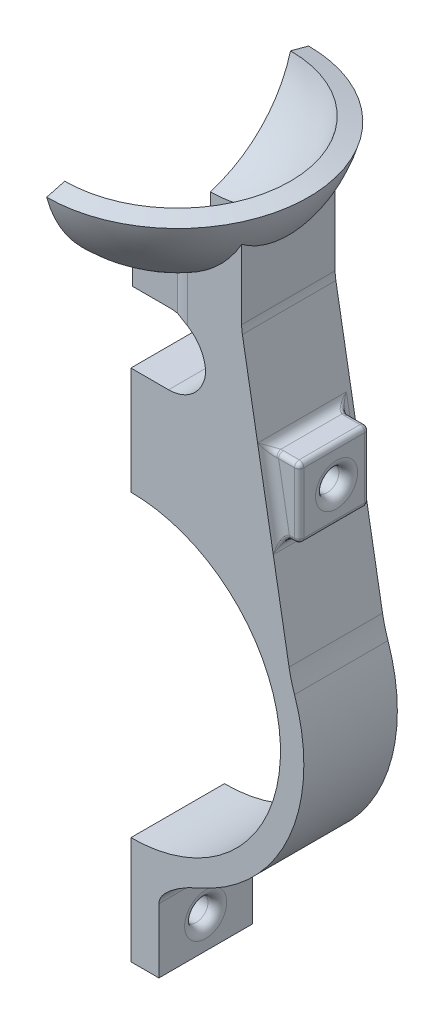
SolidWorks part; units mm, degrees
ref_plane "前视基准面" through (0, 0, 0) normal (0, 0, 1) x (1, 0, 0)
ref_plane "上视基准面" through (0, 0, 0) normal (0, 1, 0) x (1, 0, 0)
ref_plane "右视基准面" through (0, 0, 0) normal (1, 0, 0) x (0, 0, -1)
sketch "草图1" plane through (0, 0, 0) normal (0, 0, 1) x (1, 0, 0)
  line L0 (0, 0) -> (0, -170.6699) construction
  line L1 (0, -94.4259) -> (0, -92.4259)
  line L2 (12.0741, -83.1611) -> (14.0059, -83.6788)
  arc A0 (0, -94.4259) -> (14.0059, -83.6788) centre (0, -79.9259) ccw
  arc A1 (0, -92.4259) -> (12.0741, -83.1611) centre (0, -79.9259) ccw
  dimension "D1" = 29
  dimension "D2" = 25
revolve "旋转1" add sketch "草图1" angle 360 about L0
ref_plane "基准面1" through (0, -96.5, 0) normal (0, 1, 0) x (1, 0, 0)
sketch "草图2" plane through (0, -96.5, 0) normal (0, 1, 0) x (1, 0, 0)
  line L1 (4.85, -4.85) -> (-4.85, -4.85)
  line L2 (4.85, -4.85) -> (4.85, 4.85)
  line L3 (4.85, 4.85) -> (-4.85, 4.85)
  line L4 (-4.85, -4.85) -> (-4.85, 4.85)
  line L5 (-3.5, 3.5) -> (3.5, 3.5)
  line L6 (-3.5, 3.5) -> (-3.5, -3.5)
  line L7 (-3.5, -3.5) -> (3.5, -3.5)
  line L8 (3.5, 3.5) -> (3.5, -3.5)
  dimension "D1" = 4.85
  dimension "D2" = 4.85
  dimension "D3" = 9.7
  dimension "D4" = 7
  dimension "D5" = 7
  dimension "D6" = 3.5
  dimension "D7" = 3.5
extrude "凸台-拉伸1" add sketch "草图2" along normal up to next
sketch "草图3" plane through (0, -96.5, 0) normal (0, -1, 0) x (1, 0, 0)
  line L0 (3.5, -3.5) -> (-3.5, -3.5) construction
  line L1 (-3.5, -3.5) -> (-3.5, 3.5) construction
  line L2 (-3.5, 3.5) -> (3.5, 3.5) construction
  line L3 (3.5, 3.5) -> (3.5, -3.5) construction
  line L4 (3.5, -3.5) -> (-3.5, -3.5)
  line L5 (-3.5, -3.5) -> (-3.5, 3.5)
  line L6 (-3.5, 3.5) -> (3.5, 3.5)
  line L7 (3.5, 3.5) -> (3.5, -3.5)
extrude "切除-拉伸1" cut sketch "草图3" against normal up to next
sketch "草图4" plane through (0, 0, 0) normal (0, 0, 1) x (1, 0, 0)
  line L0 (0, -96.5) -> (0, -165.0033) construction
  line L1 (-4.85, -96.5) -> (4.85, -96.5) construction
  line L2 (0, -113) -> (0, -104)
  line L3 (0, -104) -> (8, -104)
  line L4 (8, -104) -> (8, -96.5)
  line L5 (8, -96.5) -> (4.85, -96.5)
  line L6 (4.85, -96.5) -> (4.85, -94.5)
  line L7 (4.85, -92.7011) -> (4.85, -96.5) construction
  line L8 (4.85, -94.5) -> (11.85, -94.5)
  line L9 (11.85, -94.5) -> (17.1515, -124.5663)
  line L10 (0, -150) -> (0, -159)
  line L11 (0, -159) -> (3, -159)
  line L12 (3, -159) -> (3, -149.7551)
  circle A0 centre (0, -131.5) radius 16
  arc A1 (0, -113) -> (0, -150) centre (0, -131.5) ccw
  arc A2 (3, -149.7551) -> (17.1515, -124.5663) centre (0, -131.5) ccw
  dimension "D1" = 35
  dimension "D2" = 32
  dimension "D3" = 2.5
  dimension "D4" = 9
  dimension "D5" = 8
  dimension "D6" = 2
  dimension "D7" = 100
  dimension "D8" = 7
  dimension "D9" = 9
  dimension "D10" = 3
extrude "凸台-拉伸2" add sketch "草图4" along normal blind 5 and the other way blind 5 separate body
sketch "草图5" plane through (0, -94.5, 0) normal (0, 1, 0) x (1, 0, 0)
  line L4 (4.85, 5) -> (4.85, -5)
  line L5 (4.85, -5) -> (11.85, -5)
  line L6 (11.85, -5) -> (11.85, 5)
  line L7 (11.85, 5) -> (4.85, 5)
  line L8 (4.85, 5) -> (4.85, -5)
  line L9 (4.85, -5) -> (11.85, -5)
  line L10 (11.85, -5) -> (11.85, 5)
  line L11 (11.85, 5) -> (4.85, 5)
  dimension "D1" = 0
fillet "圆角7" radius 6 1 edges at (3, -149.7551, 0) second distance 4 first distance on face at (13.1023, -138.8611, 0)
extrude "凸台-拉伸3" add sketch "草图5" along normal up to next
fillet "圆角1" radius 4 1 edges at (8, -96.5, 0)
fillet "圆角2" radius 4 1 edges at (8, -104, 0)
fillet "圆角3" radius 5 1 edges at (11.85, -94.5, 0)
sketch "草图6" plane through (0, 0, 0) normal (-1, 0, 0) x (0, 0, 1)
  line L0 (-5, -104) -> (5, -104) construction
  line L1 (-3.5, -105) -> (4, -105)
  line L2 (-3.5, -105) -> (-3.5, -112.5)
  line L3 (-3.5, -112.5) -> (4, -112.5)
  line L4 (4, -105) -> (4, -112.5)
  line L5 (5, -104) -> (5, -113) construction
  line L6 (-5, -104) -> (-5, -113) construction
  line L7 (-5, -113) -> (5, -113) construction
  dimension "D1" = 1
  dimension "D2" = 1
  dimension "D3" = 1.5
  dimension "D4" = 0.5
sketch "草图7" plane through (0, 0, 0) normal (0, 0, 1) x (1, 0, 0)
  line L0 (0, -160) -> (0, -67.8805) construction
  line L2 (0, -160) -> (-28.7036, -160)
  line L3 (0, -160) -> (0, -78.0888)
  line L4 (0, -78.0888) -> (-28.7036, -78.0888)
  line L5 (-28.7036, -160) -> (-28.7036, -78.0888)
  point P7 (0, 0)
extrude "切除-拉伸3" cut sketch "草图7" against normal through all both and the other way through all
fillet "圆角10" radius 5 2 edges at (4.85, -94.6172, -5) (4.85, -94.6172, 5)
extrude "凸台-拉伸4" add sketch "草图6" against normal blind 17
fillet "圆角11" radius 1 4 edges at (15.0239, -112.5, 0.25) (14.3627, -108.75, -3.5) (13.7014, -105, 0.25) (14.3627, -108.75, 4)
fillet "圆角12" radius 0.5 4 edges at (17, -112.5, 0.25) (17, -108.75, 4) (17, -105, 0.25) (17, -108.75, -3.5)
fillet "圆角13" radius 0.5 16 edges at (16.8536, -112.3536, 3.8536) (16.3578, -112.5, 4) (16.1285, -112.5038, 4) (16.8536, -112.3536, -3.3536) (16.3578, -112.5, -3.5) (16.1285, -112.5038, -3.5) (16.8536, -105.1464, -3.3536) (13.8977, -104.766, -3.8572) (14.6284, -105, -3.5038) (16.8536, -105.1464, 3.8536) (13.8977, -104.766, 4.3572) (14.6284, -105, 4.0038) (15.3965, -112.9264, 4.2929) (15.3965, -112.9264, -3.7929) (15.6084, -105, -3.5) (15.6084, -105, 4)
sketch "草图9" plane through (3, 0, 0) normal (1, 0, 0) x (0, 0, -1)
  line L0 (0, -159) -> (0, -93.1801) construction
  line L1 (5, -159) -> (-5, -159) construction
  line L2 (3, -112.5) -> (-3.5, -112.5) construction
  circle A0 centre (0, -108.8) radius 1.25
  circle A1 centre (0, -155.6) radius 1.25
  dimension "D1" = 2.5
  dimension "D2" = 2.5
  dimension "D3" = 3.7
  dimension "D4" = 3.4
extrude "切除-拉伸4" cut sketch "草图9" against normal through all both and the other way through all
fillet "圆角14" radius 15 1 edges at (17.1515, -124.5663, 0)
fillet "圆角15" radius 1 1 edges at (17, -110.05, 0)
fillet "圆角16" radius 1 1 edges at (3, -154.35, 0)
